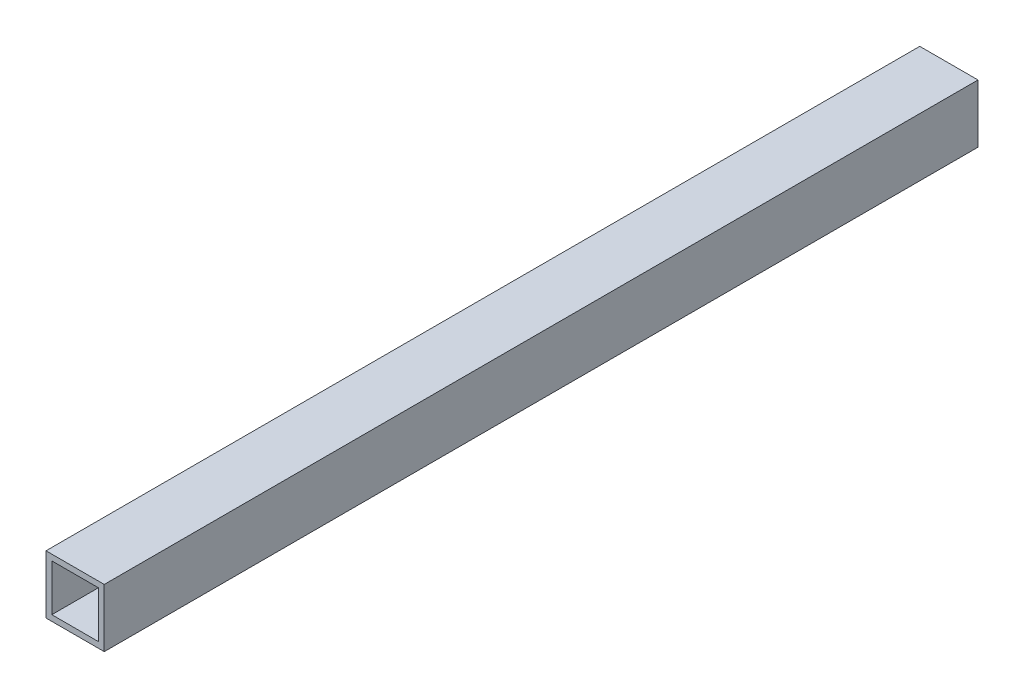
SolidWorks part; units mm, degrees
ref_plane "Płaszczyzna przednia" through (0, 0, 0) normal (0, 0, 1) x (1, 0, 0)
ref_plane "Płaszczyzna górna" through (0, 0, 0) normal (0, 1, 0) x (1, 0, 0)
ref_plane "Płaszczyzna prawa" through (0, 0, 0) normal (1, 0, 0) x (0, 0, -1)
sketch "Szkic1" plane through (0, 0, 0) normal (0, 0, 1) x (1, 0, 0)
  line L1 (-10, 10) -> (10, 10)
  line L2 (-10, 10) -> (-10, -10)
  line L3 (-10, -10) -> (10, -10)
  line L4 (10, 10) -> (10, -10)
  line L5 (-10, 10) -> (10, -10) construction
  line L6 (-10, -10) -> (10, 10) construction
  line L7 (-8, -8) -> (8, -8)
  line L8 (-8, -8) -> (-8, 8)
  line L9 (-8, 8) -> (8, 8)
  line L10 (8, -8) -> (8, 8)
  line L11 (-8, -8) -> (8, 8) construction
  line L12 (-8, 8) -> (8, -8) construction
  point P0 (0, 0)
  point P5 (0, 0)
  dimension "D1" = 20
  dimension "D2" = 16
extrude "Dodanie-wyciągnięcie1" add sketch "Szkic1" along normal blind 300
